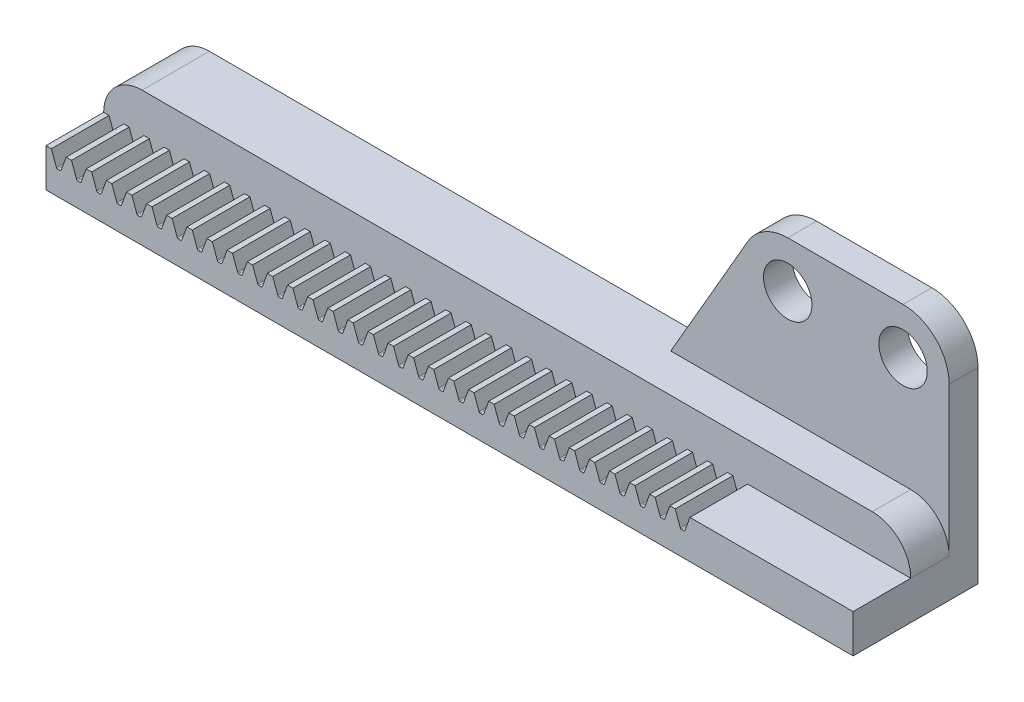
SolidWorks part; units mm, degrees
ref_plane "Front Plane" through (0, 0, 0) normal (0, 0, 1) x (1, 0, 0)
ref_plane "Top Plane" through (0, 0, 0) normal (0, 1, 0) x (1, 0, 0)
ref_plane "Right Plane" through (0, 0, 0) normal (1, 0, 0) x (0, 0, -1)
sketch "Sketch1" plane through (0, 0, 0) normal (0, 0, 1) x (1, 0, 0)
  line L0 (0, -1.5875) -> (-33.3375, -1.5875) construction
  line L1 (0, -1.5875) -> (33.3375, -1.5875) construction
  line L2 (0, -1.5875) -> (0, 1.5875) construction
  line L3 (-33.3375, 1.1811) -> (33.3375, 1.1811) construction
  line L4 (0, -1.5875) -> (3.0033, 6.664) construction
  point P3 (1185.8625, -1.5875)
  point P7 (0, 1.5875)
  dimension "Length" = 66.675
  dimension "Gear Pitch" = 1219.2
  dimension "Height" = 3.175
  dimension "Pitch Height" = 2.7686
  dimension "Pressure Angle" = 20
sketch "Sketch2" plane through (0, 0, 0) normal (1, 0, 0) x (0, 0, -1)
  line L0 (2.3813, 0) -> (-2.3813, 0) construction
  point P3 (0, 0)
  dimension "Face Width" = 4.7625
sketch "Sketch3" plane through (0, 0, 0) normal (1, 0, 0) x (0, 0, -1)
  line L0 (0, -1.5875) -> (0, 1.5875) construction
  line L1 (2.3813, 1.5875) -> (-2.3813, 1.5875)
  line L2 (0, 0) -> (-2.3813, 0) construction
  line L3 (0, 0) -> (2.3813, 0) construction
  line L4 (-2.3813, 1.5875) -> (-2.3813, -1.5875)
  line L5 (-2.3813, -1.5875) -> (2.3813, -1.5875)
  line L6 (2.3813, -1.5875) -> (2.3813, 1.5875)
extrude "Boss-Extrude1" add sketch "Sketch3" along normal up to vertex (33.3375 mm away) and the other way up to vertex (33.3375 mm away) up to point (33.3375, -1.5875, 0) other way up to point (-33.3375, -1.5875, 0)
sketch "Sketch4" plane through (0, 0, 0) normal (0, 0, 1) x (1, 0, 0)
  line L0 (-32.8915, 1.5875) -> (-32.4493, 0.3725)
  line L2 (-32.4493, 0.3725) -> (-32.1173, 0.3725)
  line L3 (-32.1173, 0.3725) -> (-31.6751, 1.5875)
  line L4 (-32.8915, 1.5875) -> (-31.6751, 1.5875)
  line L5 (-32.8915, 1.5875) -> (-33.3375, 1.5875) construction
  line L6 (-31.6751, 1.5875) -> (-31.2291, 1.5875) construction
  line L7 (-31.2291, 1.5875) -> (-30.7868, 0.3725) construction
  line L8 (-32.2833, 0.3725) -> (-32.2833, 1.5875) construction
  line L9 (-32.6989, 1.0583) -> (-31.8677, 1.0583) construction
  line L10 (-31.8677, 1.0583) -> (-31.8677, 1.5875) construction
  line L11 (-31.0365, 1.0583) -> (-31.0365, 0.3725) construction
  line L12 (-31.8677, 1.0583) -> (-31.0365, 1.0583) construction
  line L13 (-33.3375, 1.5875) -> (-33.3375, -1.5875) construction
  line L14 (33.3375, 1.5875) -> (-33.3375, 1.5875) construction
  dimension "D1" = 20
  dimension "D2" = 20
  dimension "D3" = 1.215
  dimension "D4" = 0.5292
  dimension "D5" = 1.6624
  dimension "D6" = 0.332
  dimension "D7" = 0.446
extrude "Cut-Extrude1" cut sketch "Sketch4" against normal through all both and the other way through all
fillet "Fillet1" radius 0.0996 2 edges at (-32.1173, 0.3725, 0) (-32.4493, 0.3725, 0)
pattern_linear "LPattern1" count 32 spacing 1.6624 along (1, 0, 0) of "Cut-Extrude1", "Fillet1"
sketch "Sketch6" plane through (0, 0, 0) normal (0, 0, 1) x (1, 0, 0)
  line L0 (-28.0177, 1.5875) -> (-28.0177, -1.5875) construction
  line L1 (-27.9042, 1.5875) -> (-28.3502, 1.5875) construction
  line L2 (33.3375, -1.5875) -> (-33.3375, -1.5875) construction
  line L3 (28.0177, 1.5875) -> (28.0177, -1.5875) construction
  line L5 (28.0177, 0) -> (33.3375, 0) construction
  line L6 (33.3375, 1.5875) -> (33.3375, -1.5875) construction
  line L7 (-28.0177, 0) -> (-33.3375, 0) construction
  line L8 (-33.3375, 1.5875) -> (-33.3375, -1.5875) construction
  dimension "D1" = 5.3198
sketch "Sketch8" plane through (0, 0, -2.3813) normal (0, 0, -1) x (-1, 0, 0)
  line L0 (-33.3375, -1.5875) -> (-33.3375, 1.5875)
  line L3 (-30.1625, 4.7625) -> (30.1625, 4.7625)
  line L4 (33.3375, 1.5875) -> (33.3375, -1.5875)
  line L5 (33.3375, -1.5875) -> (-33.3375, -1.5875)
  arc A2 (30.1625, 4.7625) -> (33.3375, 1.5875) centre (30.1625, 1.5875) cw
  arc A5 (-33.3375, 1.5875) -> (-30.1625, 4.7625) centre (-30.1625, 1.5875) cw
  dimension "D1" = 3.175
  dimension "D2" = 6.35
extrude "Boss-Extrude2" add sketch "Sketch8" along normal blind 5.5562
sketch "Sketch9" plane through (0, 0, -7.9375) normal (0, 0, 1) x (1, 0, 0)
  line L5 (33.3375, -1.5875) -> (6.6723, -1.5875)
  line L9 (16.7029, 15.7861) -> (6.6723, -1.5875)
  line L10 (29.5275, 17.6911) -> (20.0025, 17.6911)
  line L11 (33.3375, -1.5875) -> (33.3375, 13.8811)
  circle A5 centre (20.0025, 13.8811) radius 2
  circle A6 centre (29.5275, 13.8811) radius 2
  arc A8 (20.0025, 17.6911) -> (16.7029, 15.7861) centre (20.0025, 13.8811) ccw
  arc A9 (33.3375, 13.8811) -> (29.5275, 17.6911) centre (29.5275, 13.8811) ccw
  dimension "D1" = 9.525
  dimension "D3" = 4
  dimension "D5" = 3.81
  dimension "D2" = 15.4686
  dimension "D4" = 60
extrude "Boss-Extrude3" add sketch "Sketch9" along normal blind 2.3813
equation "\"D3@Sketch4\" =  ( 2.2 / \"Gear Pitch@Sketch1\" )  + .002"
equation "\"D4@Sketch4\" = 1 / \"Gear Pitch@Sketch1\""
equation "\"D5@Sketch4\" = 3.1416 / \"Gear Pitch@Sketch1\""
equation "\"D1@Fillet1\" = \"D6@Sketch4\" * .3"
equation "\"D3@LPattern1\" = \"D5@Sketch4\""
equation "\"D1@Sketch4\"=\"Pressure Angle@Sketch1\""
equation "\"D2@Sketch4\"=\"Pressure Angle@Sketch1\""
equation "\"D1@Sketch6\"=(3.14159/\"Gear Pitch@Sketch1\")*3.2"
